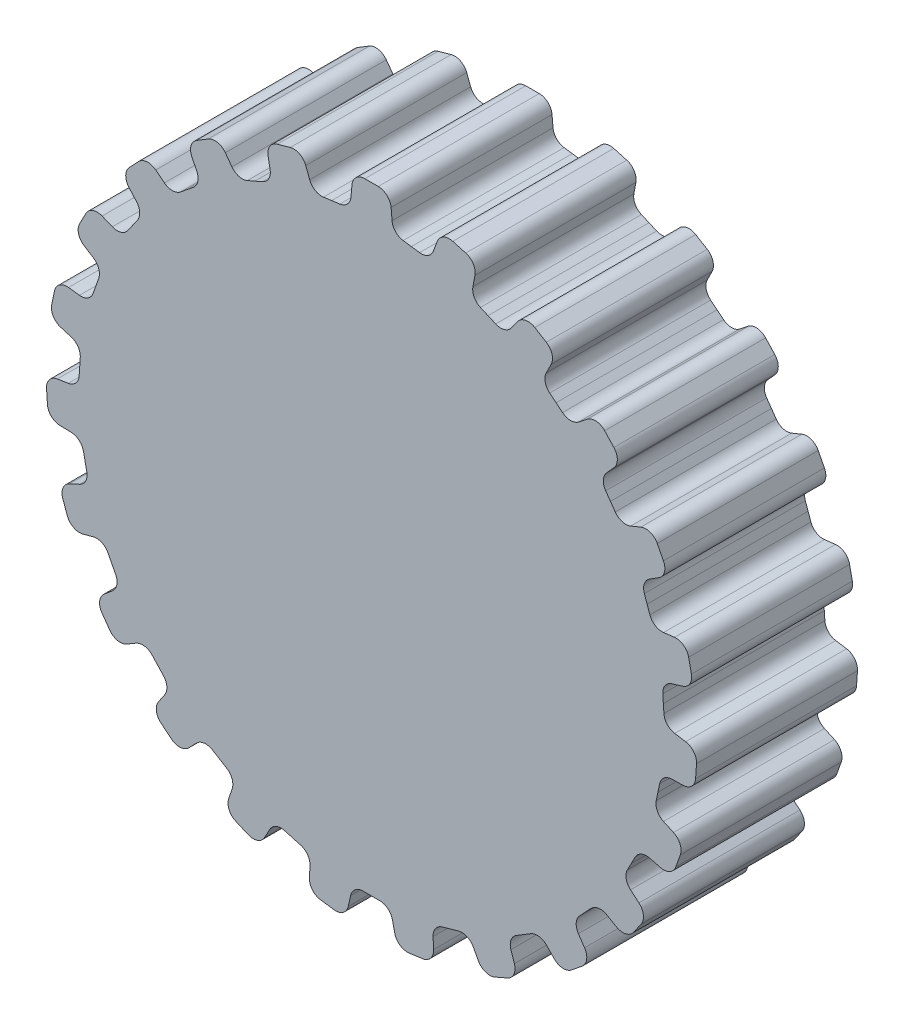
SolidWorks part; units mm, degrees
ref_plane "Front Plane" through (0, 0, 0) normal (0, 0, 1) x (1, 0, 0)
ref_plane "Top Plane" through (0, 0, 0) normal (0, 1, 0) x (1, 0, 0)
ref_plane "Right Plane" through (0, 0, 0) normal (1, 0, 0) x (0, 0, -1)
sketch "Sketch1" plane through (0, 0, 0) normal (0, 0, 1) x (1, 0, 0)
  line L0 (0, 0) -> (0, 42.8625) construction
  line L1 (0, 10.105) -> (-27.0718, 10.105) construction
  line L2 (-0.576, 10.105) -> (-0.8956, 6.4517) construction
  line L3 (-0.6656, 9.0806) -> (0, 0) construction
  line L4 (-0.6656, 9.0806) -> (-4.8277, 8.5091) construction
  line L5 (0, 0) -> (-1.2363, 9.0023) construction
  line L6 (0.2095, 10.105) -> (-0.2095, 10.105)
  line L7 (-0.6079, 9.7399) -> (-0.6378, 9.3986)
  line L8 (-0.9819, 9.0372) -> (-1.2363, 9.0023)
  line L9 (0, 25.4) -> (0, -39.6875) construction
  line L10 (0.6079, 9.7399) -> (0.6378, 9.3986)
  line L11 (0.9819, 9.0372) -> (1.2363, 9.0023)
  line L12 (1.4928, 8.967) -> (1.2384, 9.002)
  line L13 (2.0424, 9.5427) -> (1.9216, 9.2222)
  line L14 (2.928, 9.6738) -> (2.5246, 9.7868)
  line L15 (3.2132, 9.2147) -> (3.1499, 8.878)
  line L16 (3.3837, 8.4372) -> (3.6192, 8.3349)
  line L17 (3.8567, 8.2317) -> (3.6211, 8.3341)
  line L18 (4.5412, 8.6378) -> (4.3384, 8.3618)
  line L19 (5.4294, 8.5251) -> (5.0714, 8.7427)
  line L20 (5.5801, 8.006) -> (5.4283, 7.699)
  line L21 (5.5345, 7.2114) -> (5.7337, 7.0494)
  line L22 (5.9345, 6.886) -> (5.7354, 7.048)
  line L23 (6.7033, 7.0923) -> (6.4335, 6.8812)
  line L24 (7.5281, 6.7441) -> (7.2421, 7.0503)
  line L25 (7.5332, 6.2037) -> (7.3042, 5.9489)
  line L26 (7.2749, 5.4508) -> (7.423, 5.241)
  line L27 (7.5723, 5.0295) -> (7.4242, 5.2393)
  line L28 (8.3682, 5.0208) -> (8.0515, 4.8903)
  line L29 (9.0684, 4.463) -> (8.8757, 4.8349)
  line L30 (8.9276, 3.9412) -> (8.6383, 3.7577)
  line L31 (8.4757, 3.2859) -> (8.5617, 3.044)
  line L32 (8.6484, 2.8) -> (8.5625, 3.042)
  line L33 (9.4125, 2.5769) -> (9.0723, 2.5367)
  line L34 (9.9363, 1.8508) -> (9.851, 2.261)
  line L35 (9.6598, 1.3864) -> (9.3318, 1.2877)
  line L36 (9.048, 0.8774) -> (9.0655, 0.6212)
  line L37 (9.0831, 0.3628) -> (9.0657, 0.619)
  line L38 (9.7586, -0.0581) -> (9.4202, -0.0051)
  line L39 (10.0671, -0.8986) -> (10.0957, -0.4806)
  line L40 (9.6757, -1.2712) -> (9.3332, -1.2777)
  line L41 (8.9491, -1.5963) -> (8.8969, -1.8477)
  line L42 (8.8442, -2.1012) -> (8.8965, -1.8498)
  line L43 (9.3811, -2.6888) -> (9.0695, -2.5464)
  line L44 (9.4514, -3.5813) -> (9.5917, -3.1866)
  line L45 (8.9739, -3.8345) -> (8.6424, -3.7484)
  line L46 (8.1866, -3.9515) -> (8.0685, -4.1796)
  line L47 (7.9493, -4.4094) -> (8.0675, -4.1814)
  line L48 (8.3078, -5.1201) -> (8.0462, -4.8989)
  line L49 (8.1347, -5.9985) -> (8.3763, -5.6562)
  line L50 (7.6066, -6.1135) -> (7.3106, -5.9411)
  line L51 (6.8169, -6.0137) -> (6.6417, -6.2014)
  line L52 (6.4649, -6.3906) -> (6.6402, -6.203)
  line L53 (6.6183, -7.1717) -> (6.4261, -6.8881)
  line L54 (6.2147, -7.9708) -> (6.5396, -7.7064)
  line L55 (5.6751, -7.939) -> (5.4366, -7.6931)
  line L56 (4.9416, -7.6299) -> (4.7222, -7.7634)
  line L57 (4.501, -7.8979) -> (4.7204, -7.7645)
  line L58 (4.438, -8.6913) -> (4.3294, -8.3664)
  line L59 (3.8337, -9.3519) -> (4.218, -9.185)
  line L60 (3.3228, -9.1757) -> (3.1594, -8.8746)
  line L61 (2.6999, -8.6802) -> (2.4526, -8.7495)
  line L62 (2.2033, -8.8193) -> (2.4506, -8.7501)
  line L63 (1.9285, -9.5664) -> (1.9116, -9.2242)
  line L64 (1.1684, -10.0394) -> (1.5835, -9.9824)
  line L65 (0.724, -9.7319) -> (0.6479, -9.3979)
  line L66 (0.2579, -9.0867) -> (0.0011, -9.0868)
  line L67 (-0.2579, -9.0867) -> (-0.0011, -9.0868)
  line L68 (-0.724, -9.7319) -> (-0.6479, -9.3979)
  line L69 (-1.5835, -9.9824) -> (-1.1684, -10.0394)
  line L70 (-1.9285, -9.5664) -> (-1.9116, -9.2242)
  line L71 (-2.2033, -8.8193) -> (-2.4506, -8.7501)
  line L72 (-2.6999, -8.6802) -> (-2.4526, -8.7495)
  line L73 (-3.3228, -9.1757) -> (-3.1594, -8.8746)
  line L74 (-4.218, -9.185) -> (-3.8337, -9.3519)
  line L75 (-4.438, -8.6913) -> (-4.3294, -8.3664)
  line L76 (-4.501, -7.8979) -> (-4.7204, -7.7645)
  line L77 (-4.9416, -7.6299) -> (-4.7222, -7.7634)
  line L78 (-5.6751, -7.939) -> (-5.4366, -7.6931)
  line L79 (-6.5396, -7.7064) -> (-6.2147, -7.9708)
  line L80 (-6.6183, -7.1717) -> (-6.4261, -6.8881)
  line L81 (-6.4649, -6.3906) -> (-6.6402, -6.203)
  line L82 (-6.8169, -6.0137) -> (-6.6417, -6.2014)
  line L83 (-7.6066, -6.1135) -> (-7.3106, -5.9411)
  line L84 (-8.3763, -5.6562) -> (-8.1347, -5.9985)
  line L85 (-8.3078, -5.1201) -> (-8.0462, -4.8989)
  line L86 (-7.9493, -4.4094) -> (-8.0675, -4.1814)
  line L87 (-8.1866, -3.9515) -> (-8.0685, -4.1796)
  line L88 (-8.9739, -3.8345) -> (-8.6424, -3.7484)
  line L89 (-9.5917, -3.1866) -> (-9.4514, -3.5813)
  line L90 (-9.3811, -2.6888) -> (-9.0695, -2.5464)
  line L91 (-8.8442, -2.1012) -> (-8.8965, -1.8498)
  line L92 (-8.9491, -1.5963) -> (-8.8969, -1.8477)
  line L93 (-9.6757, -1.2712) -> (-9.3332, -1.2777)
  line L94 (-10.0957, -0.4806) -> (-10.0671, -0.8986)
  line L95 (-9.7586, -0.0581) -> (-9.4202, -0.0051)
  line L96 (-9.0831, 0.3628) -> (-9.0657, 0.619)
  line L97 (-9.048, 0.8774) -> (-9.0655, 0.6212)
  line L98 (-9.6598, 1.3864) -> (-9.3318, 1.2877)
  line L99 (-9.851, 2.261) -> (-9.9363, 1.8508)
  line L100 (-9.4125, 2.5769) -> (-9.0723, 2.5367)
  line L101 (-8.6484, 2.8) -> (-8.5625, 3.042)
  line L102 (-8.4757, 3.2859) -> (-8.5617, 3.044)
  line L103 (-8.9276, 3.9412) -> (-8.6383, 3.7577)
  line L104 (-8.8757, 4.8349) -> (-9.0684, 4.463)
  line L105 (-8.3682, 5.0208) -> (-8.0515, 4.8903)
  line L106 (-7.5723, 5.0295) -> (-7.4242, 5.2393)
  line L107 (-7.2749, 5.4508) -> (-7.423, 5.241)
  line L108 (-7.5332, 6.2037) -> (-7.3042, 5.9489)
  line L109 (-7.2421, 7.0503) -> (-7.5281, 6.7441)
  line L110 (-6.7033, 7.0923) -> (-6.4335, 6.8812)
  line L111 (-5.9345, 6.886) -> (-5.7354, 7.048)
  line L112 (-5.5345, 7.2114) -> (-5.7337, 7.0494)
  line L113 (-5.5801, 8.006) -> (-5.4283, 7.699)
  line L114 (-5.0714, 8.7427) -> (-5.4294, 8.5251)
  line L115 (-4.5412, 8.6378) -> (-4.3384, 8.3618)
  line L116 (-3.8567, 8.2317) -> (-3.6211, 8.3341)
  line L117 (-3.3837, 8.4372) -> (-3.6192, 8.3349)
  line L118 (-3.2132, 9.2147) -> (-3.1499, 8.878)
  line L119 (-2.5246, 9.7868) -> (-2.928, 9.6738)
  line L120 (-2.0424, 9.5427) -> (-1.9216, 9.2222)
  line L121 (-1.4928, 8.967) -> (-1.2384, 9.002)
  line L122 (-1.2363, 9.0023) -> (-1.2384, 9.002)
  line L123 (-3.6192, 8.3349) -> (-3.6211, 8.3341)
  line L124 (-5.7337, 7.0494) -> (-5.7354, 7.048)
  line L125 (-7.423, 5.241) -> (-7.4242, 5.2393)
  line L126 (-8.5617, 3.044) -> (-8.5625, 3.042)
  line L127 (-9.0655, 0.6212) -> (-9.0657, 0.619)
  line L128 (-8.8969, -1.8477) -> (-8.8965, -1.8498)
  line L130 (-8.0685, -4.1796) -> (-8.0675, -4.1814)
  line L131 (-6.6417, -6.2014) -> (-6.6402, -6.203)
  line L132 (-4.7222, -7.7634) -> (-4.7204, -7.7645)
  line L133 (-2.4526, -8.7495) -> (-2.4506, -8.7501)
  line L134 (-0.0011, -9.0868) -> (0.0011, -9.0868)
  line L135 (2.4506, -8.7501) -> (2.4526, -8.7495)
  line L136 (4.7204, -7.7645) -> (4.7222, -7.7634)
  line L137 (6.6402, -6.203) -> (6.6417, -6.2014)
  line L138 (8.0675, -4.1814) -> (8.0685, -4.1796)
  line L139 (8.8965, -1.8498) -> (8.8969, -1.8477)
  line L140 (9.0657, 0.619) -> (9.0655, 0.6212)
  line L141 (8.5625, 3.042) -> (8.5617, 3.044)
  line L142 (7.4242, 5.2393) -> (7.423, 5.241)
  line L143 (5.7354, 7.048) -> (5.7337, 7.0494)
  line L144 (3.6211, 8.3341) -> (3.6192, 8.3349)
  line L145 (1.2384, 9.002) -> (1.2363, 9.0023)
  circle A0 centre (0, 0) radius 9.105 construction
  circle A1 centre (0, 0) radius 10.105 construction
  arc A2 (-0.6079, 9.7399) -> (-0.2095, 10.105) centre (-0.2095, 9.705) cw
  arc A3 (-0.6378, 9.3986) -> (-0.9819, 9.0372) centre (-1.0363, 9.4335) cw
  arc A4 (0.6079, 9.7399) -> (0.2095, 10.105) centre (0.2095, 9.705) ccw
  arc A5 (0.6378, 9.3986) -> (0.9819, 9.0372) centre (1.0363, 9.4335) ccw
  arc A6 (1.9216, 9.2222) -> (1.4928, 8.967) centre (1.5473, 9.3633) cw
  arc A7 (2.0424, 9.5427) -> (2.5246, 9.7868) centre (2.4167, 9.4016) cw
  arc A8 (3.2132, 9.2147) -> (2.928, 9.6738) centre (2.8201, 9.2886) ccw
  arc A9 (3.1499, 8.878) -> (3.3837, 8.4372) centre (3.543, 8.8041) ccw
  arc A10 (4.3384, 8.3618) -> (3.8567, 8.2317) centre (4.0161, 8.5986) cw
  arc A11 (4.5412, 8.6378) -> (5.0714, 8.7427) centre (4.8636, 8.401) cw
  arc A12 (5.5801, 8.006) -> (5.4294, 8.5251) centre (5.2215, 8.1833) ccw
  arc A13 (5.4283, 7.699) -> (5.5345, 7.2114) centre (5.7869, 7.5217) ccw
  arc A14 (6.4335, 6.8812) -> (5.9345, 6.886) centre (6.187, 7.1962) cw
  arc A15 (6.7033, 7.0923) -> (7.2421, 7.0503) centre (6.9498, 6.7773) cw
  arc A16 (7.5332, 6.2037) -> (7.5281, 6.7441) centre (7.2357, 6.4711) ccw
  arc A17 (7.3042, 5.9489) -> (7.2749, 5.4508) centre (7.6016, 5.6815) ccw
  arc A18 (8.0515, 4.8903) -> (7.5723, 5.0295) centre (7.8991, 5.2601) cw
  arc A19 (8.3682, 5.0208) -> (8.8757, 4.8349) centre (8.5206, 4.6509) cw
  arc A20 (8.9276, 3.9412) -> (9.0684, 4.463) centre (8.7133, 4.2789) ccw
  arc A21 (8.6383, 3.7577) -> (8.4757, 3.2859) centre (8.8526, 3.4199) ccw
  arc A22 (9.0723, 2.5367) -> (8.6484, 2.8) centre (9.0253, 2.9339) cw
  arc A23 (9.4125, 2.5769) -> (9.851, 2.261) centre (9.4594, 2.1796) cw
  arc A24 (9.6598, 1.3864) -> (9.9363, 1.8508) centre (9.5446, 1.7695) ccw
  arc A25 (9.3318, 1.2877) -> (9.048, 0.8774) centre (9.447, 0.9047) ccw
  arc A26 (9.4202, -0.0051) -> (9.0831, 0.3628) centre (9.4822, 0.3901) cw
  arc A27 (9.7586, -0.0581) -> (10.0957, -0.4806) centre (9.6967, -0.4533) cw
  arc A28 (9.6757, -1.2712) -> (10.0671, -0.8986) centre (9.6681, -0.8713) ccw
  arc A29 (9.3332, -1.2777) -> (8.9491, -1.5963) centre (9.3408, -1.6776) ccw
  arc A30 (9.0695, -2.5464) -> (8.8442, -2.1012) centre (9.2358, -2.1826) cw
  arc A31 (9.3811, -2.6888) -> (9.5917, -3.1866) centre (9.2148, -3.0526) cw
  arc A32 (8.9739, -3.8345) -> (9.4514, -3.5813) centre (9.0745, -3.4474) ccw
  arc A33 (8.6424, -3.7484) -> (8.1866, -3.9515) centre (8.5418, -4.1355) ccw
  arc A34 (8.0462, -4.8989) -> (7.9493, -4.4094) centre (8.3045, -4.5935) cw
  arc A35 (8.3078, -5.1201) -> (8.3763, -5.6562) centre (8.0495, -5.4256) cw
  arc A36 (7.6066, -6.1135) -> (8.1347, -5.9985) centre (7.8079, -5.7678) ccw
  arc A37 (7.3106, -5.9411) -> (6.8169, -6.0137) centre (7.1093, -6.2867) ccw
  arc A38 (6.4261, -6.8881) -> (6.4649, -6.3906) centre (6.7572, -6.6637) cw
  arc A39 (6.6183, -7.1717) -> (6.5396, -7.7064) centre (6.2872, -7.3961) cw
  arc A40 (5.6751, -7.939) -> (6.2147, -7.9708) centre (5.9622, -7.6605) ccw
  arc A41 (5.4366, -7.6931) -> (4.9416, -7.6299) centre (5.1495, -7.9716) ccw
  arc A42 (4.3294, -8.3664) -> (4.501, -7.8979) centre (4.7088, -8.2396) cw
  arc A43 (4.438, -8.6913) -> (4.218, -9.185) centre (4.0586, -8.8181) cw
  arc A44 (3.3228, -9.1757) -> (3.8337, -9.3519) centre (3.6744, -8.985) ccw
  arc A45 (3.1594, -8.8746) -> (2.6999, -8.6802) centre (2.8078, -9.0654) ccw
  arc A46 (1.9116, -9.2242) -> (2.2033, -8.8193) centre (2.3112, -9.2045) cw
  arc A47 (1.9285, -9.5664) -> (1.5835, -9.9824) centre (1.529, -9.5861) cw
  arc A48 (0.724, -9.7319) -> (1.1684, -10.0394) centre (1.114, -9.6431) ccw
  arc A49 (0.6479, -9.3979) -> (0.2579, -9.0867) centre (0.2579, -9.4867) ccw
  arc A50 (-0.6479, -9.3979) -> (-0.2579, -9.0867) centre (-0.2579, -9.4867) cw
  arc A51 (-0.724, -9.7319) -> (-1.1684, -10.0394) centre (-1.114, -9.6431) cw
  arc A52 (-1.9285, -9.5664) -> (-1.5835, -9.9824) centre (-1.529, -9.5861) ccw
  arc A53 (-1.9116, -9.2242) -> (-2.2033, -8.8193) centre (-2.3112, -9.2045) ccw
  arc A54 (-3.1594, -8.8746) -> (-2.6999, -8.6802) centre (-2.8078, -9.0654) cw
  arc A55 (-3.3228, -9.1757) -> (-3.8337, -9.3519) centre (-3.6744, -8.985) cw
  arc A56 (-4.438, -8.6913) -> (-4.218, -9.185) centre (-4.0586, -8.8181) ccw
  arc A57 (-4.3294, -8.3664) -> (-4.501, -7.8979) centre (-4.7088, -8.2396) ccw
  arc A58 (-5.4366, -7.6931) -> (-4.9416, -7.6299) centre (-5.1495, -7.9716) cw
  arc A59 (-5.6751, -7.939) -> (-6.2147, -7.9708) centre (-5.9622, -7.6605) cw
  arc A60 (-6.6183, -7.1717) -> (-6.5396, -7.7064) centre (-6.2872, -7.3961) ccw
  arc A61 (-6.4261, -6.8881) -> (-6.4649, -6.3906) centre (-6.7572, -6.6637) ccw
  arc A62 (-7.3106, -5.9411) -> (-6.8169, -6.0137) centre (-7.1093, -6.2867) cw
  arc A63 (-7.6066, -6.1135) -> (-8.1347, -5.9985) centre (-7.8079, -5.7678) cw
  arc A64 (-8.3078, -5.1201) -> (-8.3763, -5.6562) centre (-8.0495, -5.4256) ccw
  arc A65 (-8.0462, -4.8989) -> (-7.9493, -4.4094) centre (-8.3045, -4.5935) ccw
  arc A66 (-8.6424, -3.7484) -> (-8.1866, -3.9515) centre (-8.5418, -4.1355) cw
  arc A67 (-8.9739, -3.8345) -> (-9.4514, -3.5813) centre (-9.0745, -3.4474) cw
  arc A68 (-9.3811, -2.6888) -> (-9.5917, -3.1866) centre (-9.2148, -3.0526) ccw
  arc A69 (-9.0695, -2.5464) -> (-8.8442, -2.1012) centre (-9.2358, -2.1826) ccw
  arc A70 (-9.3332, -1.2777) -> (-8.9491, -1.5963) centre (-9.3408, -1.6776) cw
  arc A71 (-9.6757, -1.2712) -> (-10.0671, -0.8986) centre (-9.6681, -0.8713) cw
  arc A72 (-9.7586, -0.0581) -> (-10.0957, -0.4806) centre (-9.6967, -0.4533) ccw
  arc A73 (-9.4202, -0.0051) -> (-9.0831, 0.3628) centre (-9.4822, 0.3901) ccw
  arc A74 (-9.3318, 1.2877) -> (-9.048, 0.8774) centre (-9.447, 0.9047) cw
  arc A75 (-9.6598, 1.3864) -> (-9.9363, 1.8508) centre (-9.5446, 1.7695) cw
  arc A76 (-9.4125, 2.5769) -> (-9.851, 2.261) centre (-9.4594, 2.1796) ccw
  arc A77 (-9.0723, 2.5367) -> (-8.6484, 2.8) centre (-9.0253, 2.9339) ccw
  arc A78 (-8.6383, 3.7577) -> (-8.4757, 3.2859) centre (-8.8526, 3.4199) cw
  arc A79 (-8.9276, 3.9412) -> (-9.0684, 4.463) centre (-8.7133, 4.2789) cw
  arc A80 (-8.3682, 5.0208) -> (-8.8757, 4.8349) centre (-8.5206, 4.6509) ccw
  arc A81 (-8.0515, 4.8903) -> (-7.5723, 5.0295) centre (-7.8991, 5.2601) ccw
  arc A82 (-7.3042, 5.9489) -> (-7.2749, 5.4508) centre (-7.6016, 5.6815) cw
  arc A83 (-7.5332, 6.2037) -> (-7.5281, 6.7441) centre (-7.2357, 6.4711) cw
  arc A84 (-6.7033, 7.0923) -> (-7.2421, 7.0503) centre (-6.9498, 6.7773) ccw
  arc A85 (-6.4335, 6.8812) -> (-5.9345, 6.886) centre (-6.187, 7.1962) ccw
  arc A86 (-5.4283, 7.699) -> (-5.5345, 7.2114) centre (-5.7869, 7.5217) cw
  arc A87 (-5.5801, 8.006) -> (-5.4294, 8.5251) centre (-5.2215, 8.1833) cw
  arc A88 (-4.5412, 8.6378) -> (-5.0714, 8.7427) centre (-4.8636, 8.401) ccw
  arc A89 (-4.3384, 8.3618) -> (-3.8567, 8.2317) centre (-4.0161, 8.5986) ccw
  arc A90 (-3.1499, 8.878) -> (-3.3837, 8.4372) centre (-3.543, 8.8041) cw
  arc A91 (-3.2132, 9.2147) -> (-2.928, 9.6738) centre (-2.8201, 9.2886) cw
  arc A92 (-2.0424, 9.5427) -> (-2.5246, 9.7868) centre (-2.4167, 9.4016) ccw
  arc A93 (-1.9216, 9.2222) -> (-1.4928, 8.967) centre (-1.5473, 9.3633) ccw
  point P4 (0, 10.105)
  point P8 (-0.576, 10.105)
  point P11 (-0.6656, 9.0806)
  point P13 (-1.2363, 9.0023)
  dimension "DIA" = 18.21
  dimension "D2" = 20.21
  dimension "D6" = 0.4
  dimension "D7" = 0.4
  dimension "D3" = 0.576
  dimension "SIZE" = 0.576
  dimension "D4" = 95
  dimension "D5" = 90
extrude "Extrude1" add sketch "Sketch1" along normal blind 5
equation "\"D3@Sketch1\" = \"SIZE\""
equation "\"D2@Sketch1\" = \"DIA\"+2"
